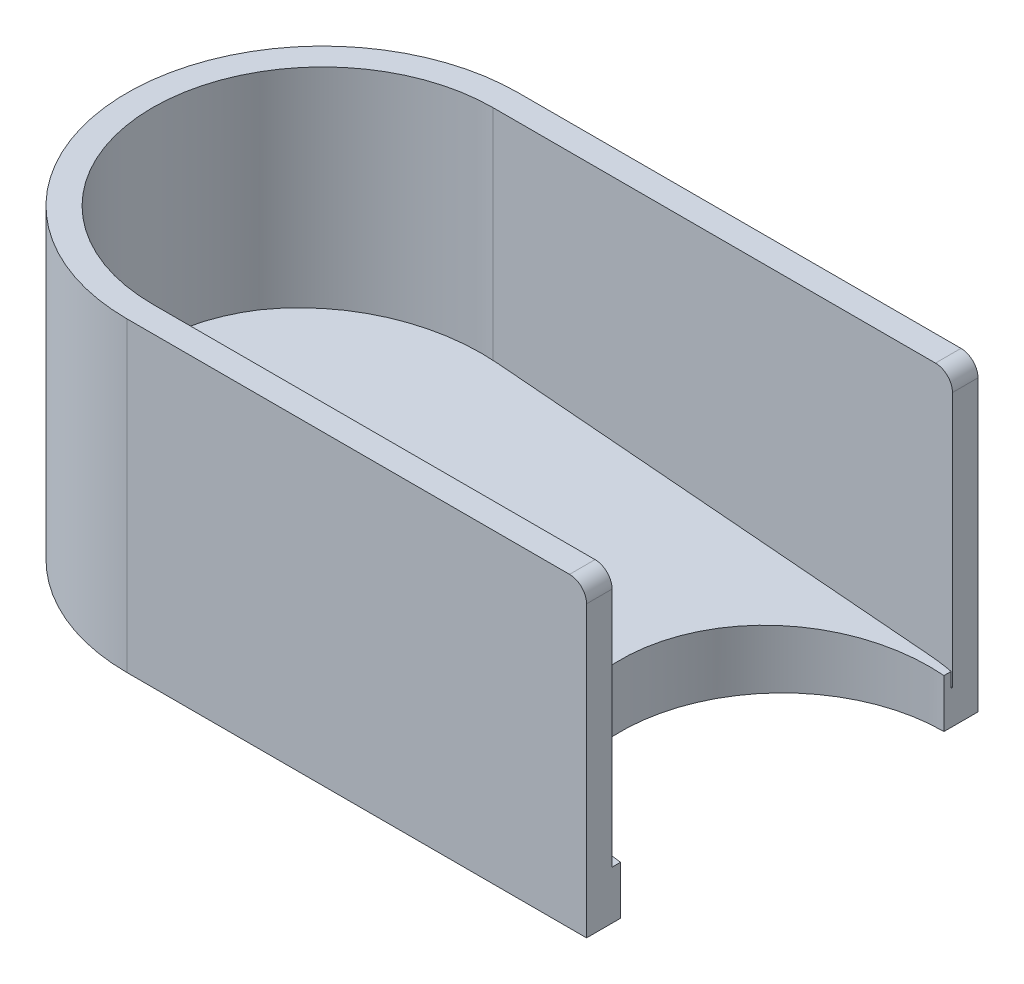
SolidWorks part; units mm, degrees
ref_plane "Front Plane" through (0, 0, 0) normal (0, 0, 1) x (1, 0, 0)
ref_plane "Top Plane" through (0, 0, 0) normal (0, 1, 0) x (1, 0, 0)
ref_plane "Right Plane" through (0, 0, 0) normal (1, 0, 0) x (0, 0, -1)
sketch "Sketch3" plane through (0, 0, 0) normal (0, 1, 0) x (1, 0, 0)
  line L0 (-13.5, 0) -> (13.5, 0) construction
  line L2 (-13.5, 11.5) -> (13.5, 11.5)
  line L3 (-13.5, -11.5) -> (13.5, -11.5)
  arc A0 (-13.5, 11.5) -> (-13.5, -11.5) centre (-13.5, 0) ccw
  arc A1 (13.5, -11.5) -> (13.5, 11.5) centre (13.5, 0) ccw
  point P5 (0, 0)
extrude "Main Body" add sketch "Sketch3" along normal blind 18
sketch "Sketch4" plane through (0, 18, 0) normal (0, 1, 0) x (1, 0, 0)
  line L0 (-13.5, 0) -> (13.5, 0) construction
  line L2 (-13.5, 10) -> (13.5, 10)
  line L3 (-13.5, -10) -> (13.5, -10)
  arc A0 (-13.5, 10) -> (-13.5, -10) centre (-13.5, 0) ccw
  arc A1 (13.5, -10) -> (13.5, 10) centre (13.5, 0) ccw
  point P5 (0, 0)
extrude "Slot Cut" cut sketch "Sketch4" against normal blind 16
sketch "line for vertical plane" plane through (0, 18, 0) normal (0, 1, 0) x (1, 0, 0)
  line L0 (-23.5, 0) -> (-23.5, 13.5143) construction
  arc A0 (-13.5, 10) -> (-13.5, -10) centre (-13.5, 0) ccw construction
sketch3d "Vertical plane"
sketch "Lines for slant plane" plane through (-23.5, 0, 0) normal (1, 0, 0) x (0, 0, -1)
  line L0 (0, 2) -> (0, 6) construction
  line L2 (0, 6) -> (4, 6) construction
  dimension "D1" = 4
  dimension "D2" = 4
sketch3d "Slant Plane"
  arc A0 (13.5, 2, 10) -> (13.5, 2, -10) centre (13.5, 2, 0) ccw construction
  point P2 (23.5, 2, 0)
  point P7 (13.5, 12, 0)
sketch "Sketch7" plane through (0.338, 3.9712, 0) normal (0.0848, 0.9964, 0) x (0.9964, -0.0848, 0)
  line L0 (-13.621, 10) -> (11.925, 10)
  line L1 (13.2818, 10) -> (-13.621, 10) construction
  line L2 (11.925, -11.0463) -> (-13.621, -11.0463)
  arc A0 (11.925, 10) -> (11.925, -11.0463) centre (11.925, -0.5232) cw
  arc A1 (-13.621, -11.0463) -> (-13.621, 10) centre (-13.621, -0.5232) cw
  ellipse E0 centre (11.925, 0) end of major axis (11.925, 10) minor radius 9.964 (11.925, -10) -> (11.925, 10) ccw construction
extrude "Ramp" add sketch "Sketch7" against normal blind 10
sketch "Sketch9" plane through (0, 0, 0) normal (0, 1, 0) x (1, 0, 0)
  line L1 (-27.0579, 16.5815) -> (27.7592, 16.5815)
  line L2 (-27.0579, 16.5815) -> (-27.0579, -15.2077)
  line L3 (-27.0579, -15.2077) -> (27.7592, -15.2077)
  line L4 (27.7592, 16.5815) -> (27.7592, -15.2077)
extrude "Flat Base" cut sketch "Sketch9" against normal blind 10
sketch "Exit" plane through (0, 0, 0) normal (0, -1, 0) x (1, 0, 0)
  line L0 (0, 0) -> (13.5, 0) construction
  circle A0 centre (13.5, 0) radius 9.5
  dimension "D2" = 19
  dimension "D1" = 13.5
extrude "Exit Hole" cut sketch "Exit" against normal blind 10
sketch "Attach" plane through (0, 0, 0) normal (0, -1, 0) x (1, 0, 0)
  line L0 (0, 0) -> (-13.5, 0) construction
  circle A0 centre (-13.5, 0) radius 2.56
  dimension "D2" = 5.12
  dimension "D1" = 13.5
extrude "Attach point" cut sketch "Attach" against normal blind 4
sketch3d "Correction Plane"
  line L0 (13.5, 2, -10) -> (13.5, 18, -10) construction
  line L1 (13.5, 18, 11.5) -> (13.5, 0, 11.5) construction
sketch "Sketch10" plane through (13.5, 0, 0) normal (-1, 0, 0) x (0, 0, 1)
  line L1 (12.2227, 18.5285) -> (-12.7645, 18.5285)
  line L2 (12.2227, 18.5285) -> (12.2227, -1.3458)
  line L3 (12.2227, -1.3458) -> (-12.7645, -1.3458)
  line L4 (-12.7645, 18.5285) -> (-12.7645, -1.3458)
extrude "Correction Cut" cut sketch "Sketch10" against normal blind 15
fillet "Smooth Edges" radius 1 2 edges at (13.5, 18, -10.75) (13.5, 18, 10.75)
